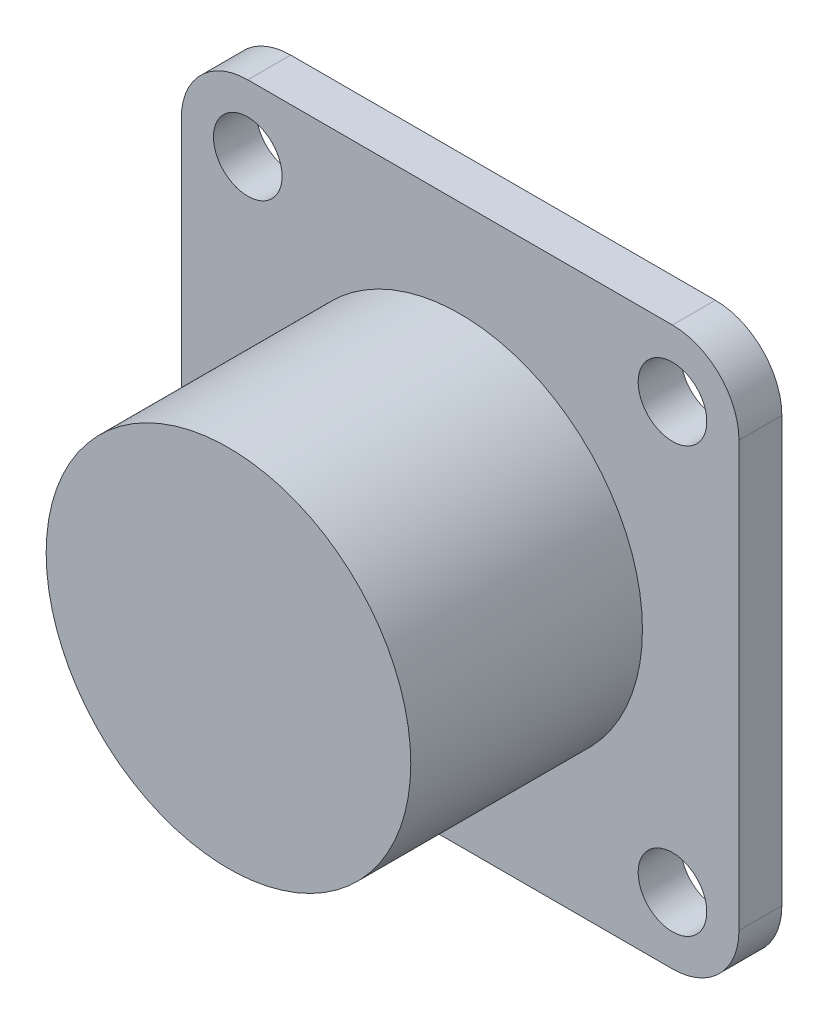
SolidWorks part; units mm, degrees
ref_plane "Front Plane" through (0, 0, 0) normal (0, 0, 1) x (1, 0, 0)
ref_plane "Top Plane" through (0, 0, 0) normal (0, 1, 0) x (1, 0, 0)
ref_plane "Right Plane" through (0, 0, 0) normal (1, 0, 0) x (0, 0, -1)
sketch "Sketch1" plane through (0, 0, 0) normal (0, 0, 1) x (1, 0, 0)
  line L1 (-13, -13) -> (13, -13)
  line L2 (-13, -13) -> (-13, 13)
  line L3 (-13, 13) -> (13, 13)
  line L4 (13, -13) -> (13, 13)
  line L5 (-13, -13) -> (13, 13) construction
  line L6 (-13, 13) -> (13, -13) construction
  point P0 (0, 0)
  point P8 (-10.9, -8.6866)
  point P9 (0, 0)
  point P17 (0, 0)
  dimension "D2" = 26
extrude "Boss-Extrude1" add sketch "Sketch1" along normal blind 2
fillet "Fillet1" radius 3.1 4 edges at (13, 13, 1) (13, -13, 1) (-13, -13, 1) (-13, 13, 1)
sketch "Sketch3" plane through (0, 0, 0) normal (0, 0, 1) x (1, 0, 0)
  circle A0 centre (0, 0) radius 8.5
  dimension "D1" = 17
extrude "Boss-Extrude2" add sketch "Sketch3" along normal blind 12.8
hole_wizard "M3 Clearance Hole1" positions "Sketch5" profile "Sketch6" hole size "M3" standard "ISO"
sketch "Sketch5" plane through (0, 0, 0) normal (0, 0, -1) x (-1, 0, 0)
  point P14 (9.9, 9.9)
  point P17 (9.9, -9.9)
  point P20 (-9.9, -9.9)
  point P25 (-9.9, 9.9)
sketch "Sketch6" plane through (-9.9, 9.9, 0) normal (1, 0, 0) x (0, 1, 0)
  line L0 (0, 0) -> (0, 5.9614)
  line L1 (0, 5.9614) -> (1.6, 5)
  line L2 (1.6, 5) -> (1.6, 0)
  line L5 (1.6, 0) -> (0, 0)
  line L10 (0, 5.9614) -> (-1.6, 5) construction
  line L11 (0, -6.35) -> (0, 107.95) construction
  dimension "Hole Dia." = 3.2
  dimension "Hole Depth" = 5
  dimension "Drill Angle" = 118
ref_axis "Axis1" through (0, 0, 13.44) along (0, 0, -1)
sketch "Sketch7" plane through (0, 0, 0) normal (0, 0, -1) x (-1, 0, 0)
  circle A0 centre (0, 0) radius 5.85
  circle A1 centre (0, 0) radius 8
  dimension "D1" = 11.7
  dimension "D2" = 16
extrude "Cut-Extrude1" cut sketch "Sketch7" against normal offset from surface (11.8 mm away) 1 up to face at (8.5, 0, 12.8)
